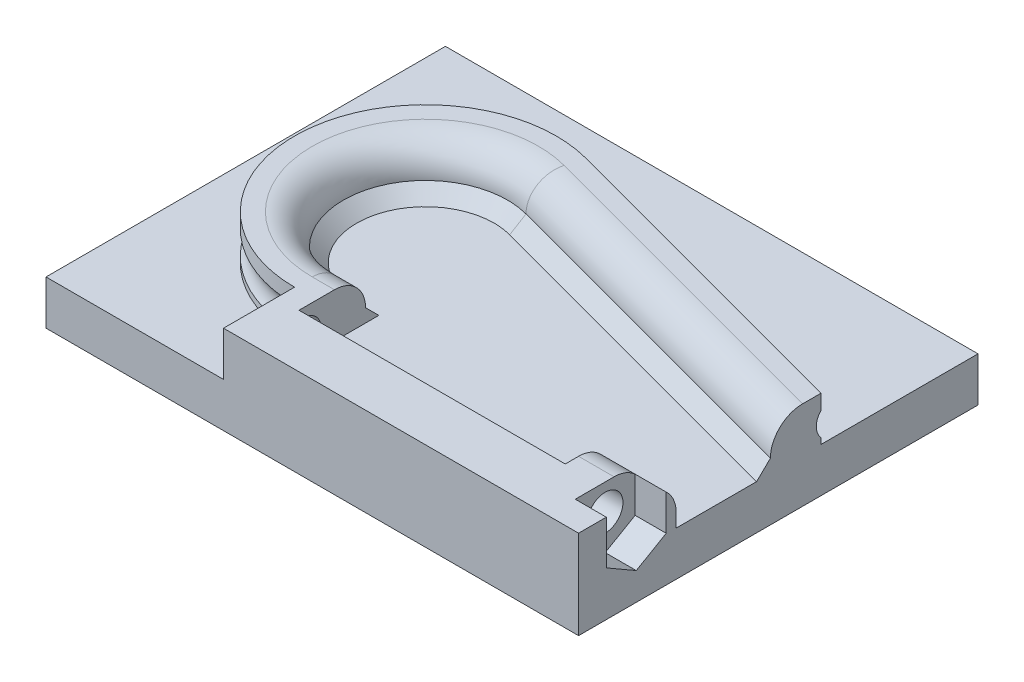
SolidWorks part; units mm, degrees
other "Camera1"
ref_plane "Front Plane" through (0, 0, 0) normal (0, 0, 1) x (1, 0, 0)
ref_plane "Top Plane" through (0, 0, 0) normal (0, 1, 0) x (1, 0, 0)
ref_plane "Right Plane" through (0, 0, 0) normal (1, 0, 0) x (0, 0, -1)
sketch "Sketch1" plane through (0, 0, 0) normal (0, 1, 0) x (1, 0, 0)
  line L1 (-60, 45) -> (60, 45)
  line L2 (-60, 45) -> (-60, -45)
  line L3 (-60, -45) -> (60, -45)
  line L4 (60, 45) -> (60, -45)
  line L5 (-60, 45) -> (60, -45) construction
  line L6 (-60, -45) -> (60, 45) construction
  point P0 (0, 0)
  dimension "D1" = 120
  dimension "D2" = 90
extrude "Boss-Extrude1" add sketch "Sketch1" along normal blind 10
sketch "Sketch2" plane through (0, 10, 0) normal (0, 1, 0) x (1, 0, 0)
  line L0 (-20, -29) -> (-73.0657, -29) construction
  line L1 (60, -45) -> (-20, -45)
  line L2 (60, -45) -> (60, -29)
  line L4 (-20, -45) -> (-20, -29)
  line L5 (-20, -24) -> (-20, 30) construction
  line L6 (60, 9.6047) -> (-12.3648, 28.9948)
  line L7 (60, -45) -> (60, 45) construction
  line L8 (60, 9.6047) -> (60, -29)
  arc A0 (-12.3648, 28.9948) -> (-20, -29) centre (-20, 0.5) ccw
  dimension "D2" = 59
  dimension "D3" = 75
  dimension "D4" = 80
  dimension "D1" = 16
  dimension "D5" = 16
extrude "Boss-Extrude2" add sketch "Sketch2" along normal blind 10
sketch "Sketch3" plane through (60, 0, 0) normal (1, 0, 0) x (0, 0, -1)
  line L0 (9.6047, 10) -> (-48.4082, 10) construction
  line L1 (-45, 20) -> (-45, 0) construction
  circle A0 centre (-32, 14) radius 4
  dimension "D1" = 8
  dimension "D2" = 4
  dimension "D3" = 13
ref_plane "Plane1" through (0, 14, 0) normal (0, 1, 0) x (1, 0, 0)
sketch "Sketch4" plane through (0, 14, 0) normal (0, 1, 0) x (1, 0, 0)
  line L0 (60, -32) -> (-20, -32)
  line L1 (60, -36) -> (60, -28) construction
  line L2 (60, 12.7105) -> (-11.5884, 31.8926)
  line L3 (60, 9.6047) -> (-12.3648, 28.9948) construction
  line L4 (60, 9.6047) -> (60, 45) construction
  line L8 (60, 12.7105) -> (80.9753, 7.0902)
  arc A0 (-20, -32) -> (-11.5884, 31.8926) centre (-20, 0.5) cw
  dimension "D1" = 32.5
  dimension "D2" = 3
  dimension "D3" = 3
  dimension "D4" = 21.7153
sweep "Cut-Sweep1" cut profiles "Sketch3" path "Sketch4"
sketch "Sketch5" plane through (0, 20, 0) normal (0, 1, 0) x (1, 0, 0)
  line L0 (-15, -18) -> (-15, -33)
  line L1 (-15, -33) -> (45, -33)
  line L2 (60, -23) -> (60, -1.7833)
  line L3 (60, 9.6047) -> (-12.3648, 28.9948) construction
  line L4 (-20, -29) -> (-20, -45) construction
  line L5 (60, -45) -> (60, 9.6047) construction
  line L6 (45, -33) -> (45, -23)
  line L7 (45, -23) -> (60, -23)
  line L8 (-20, -18) -> (-15, -18)
  line L10 (-15.2118, 18.3696) -> (60, -1.7833)
  line L12 (49, -34) -> (49, 1.1641)
  line L13 (49, 1.1641) -> (-15.2118, 18.3696)
  line L14 (-9, -14.3745) -> (-9, -34)
  line L15 (-9, -34) -> (49, -34)
  arc A3 (-15.2118, 18.3696) -> (-9, -14.3745) centre (-20, 0.5) ccw
  arc A4 (-15.2118, 18.3696) -> (-20, -18) centre (-20, 0.5) ccw
  point P0 (-15, -18)
  dimension "D4" = 15
  dimension "D2" = 5
  dimension "D3" = 15
  dimension "D5" = 10
  dimension "D1" = 11
extrude "Cut-Extrude1" cut sketch "Sketch5" against normal blind 10
chamfer "Chamfer2" distance 3 angle 45 3 edges at (-17.5, 10, 18) (22.3941, 10, -8.2932) (-38.3417, 10, -2.9147)
fillet "Fillet1" radius 7 4 edges at (-17.5, 20, 18) (-38.3417, 20, -2.9147) (22.3941, 20, -8.2932) (52.5, 20, 23)
sketch "Sketch6" plane through (60, 0, 0) normal (1, 0, 0) x (0, 0, -1)
  line L1 (-32, 6.2058) -> (-25.25, 10.1029)
  line L6 (-38.75, 10.1029) -> (-32, 6.2058)
  line L7 (-45, 20) -> (-45, 0) construction
  line L11 (-35.1077, 20) -> (-35.375, 19.8457) [skipped]
  line L12 (-26.4599, 18.5957) -> (-26.7272, 18.75) [skipped]
  line L13 (-38.75, 17.8971) -> (-38.75, 10.1029) [skipped]
  line L14 (-25.25, 10.1029) -> (-25.25, 17.8971) [skipped]
  line L15 (-38.75, 10.1029) -> (-38.75, 20)
  line L16 (-45, 20) -> (-30, 20) construction
  line L17 (-38.75, 20) -> (-25.25, 20)
  line L18 (-25, 20) -> (-33, 20) construction
  line L19 (-25.25, 20) -> (-25.25, 10.1029)
  dimension "D1" = 13.5
  dimension "D2" = 9.8971
  dimension "D3" = 9.8971
  dimension "D4" = 7.7942
  dimension "D5" = 6.25
extrude "Cut-Extrude2" cut sketch "Sketch6" against normal blind 7
